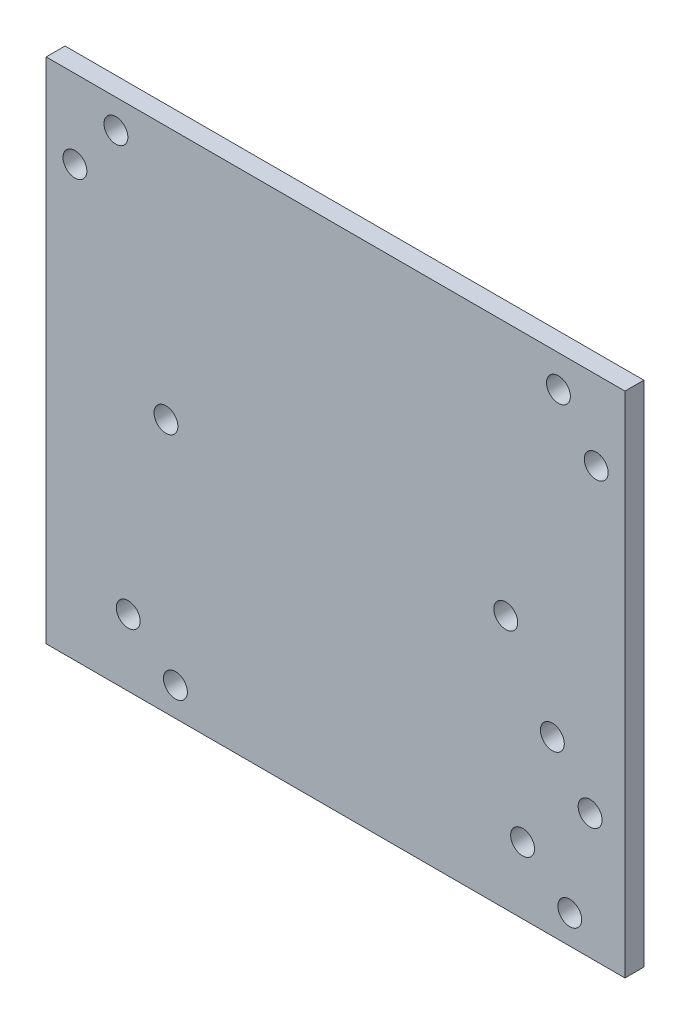
SolidWorks part; units mm, degrees
ref_plane "Front Plane" through (0, 0, 0) normal (0, 0, 1) x (1, 0, 0)
ref_plane "Top Plane" through (0, 0, 0) normal (0, 1, 0) x (1, 0, 0)
ref_plane "Right Plane" through (0, 0, 0) normal (1, 0, 0) x (0, 0, -1)
sketch "Sketch1" plane through (0, 0, 0) normal (0, 0, 1) x (1, 0, 0)
  line L0 (959.4886, 308.695) -> (959.4886, 257.3944) construction
  line L1 (959.4886, 234.6614) -> (959.4886, 406.5207) construction
  line L2 (862.0448, 217.2783) -> (1056.7178, 217.2783)
  line L3 (862.0448, 217.2783) -> (862.0448, 388.2332)
  line L4 (862.0448, 388.2332) -> (1056.7178, 388.2332)
  line L5 (1056.7178, 217.2783) -> (1056.7178, 388.2332)
  line L6 (902.3386, 302.7557) -> (1016.6386, 302.7557) construction
  circle A0 centre (1022.28, 239.6533) radius 2.5273 construction
  circle A1 centre (1038.155, 226.9533) radius 2.5273 construction
  circle A2 centre (889.6448, 239.6533) radius 2.5273 construction
  circle A3 centre (1034.3339, 377.4809) radius 2.5273 construction
  circle A4 centre (1047.0428, 361.6131) radius 2.5273 construction
  circle A5 centre (871.7198, 361.7933) radius 2.5273 construction
  circle A6 centre (885.5053, 378.5582) radius 2.5273 construction
  circle A7 centre (1022.28, 239.6533) radius 2.5273 construction
  circle A8 centre (1038.155, 226.9533) radius 2.5273 construction
  circle A9 centre (889.6448, 239.6533) radius 2.5273 construction
  circle A10 centre (1034.3339, 377.4809) radius 2.5273 construction
  circle A11 centre (1047.0428, 361.6131) radius 2.5273 construction
  circle A12 centre (871.7198, 361.7933) radius 2.5273 construction
  circle A13 centre (885.5053, 378.5582) radius 2.5273 construction
  circle A14 centre (905.5198, 226.9533) radius 2.5273 construction
  circle A15 centre (905.5198, 226.9533) radius 2.5273 construction
  circle A16 centre (1022.28, 239.6533) radius 4.0127
  circle A17 centre (1038.155, 226.9533) radius 4.0127
  circle A18 centre (889.6448, 239.6533) radius 4.0127
  circle A19 centre (1034.3339, 377.4809) radius 4.0127
  circle A20 centre (1047.0428, 361.6131) radius 4.0127
  circle A21 centre (871.7198, 361.7933) radius 4.0127
  circle A22 centre (885.5053, 378.5582) radius 4.0127
  circle A23 centre (905.5198, 226.9533) radius 4.0127
  circle A24 centre (885.5053, 378.5582) radius 6.5 construction
  circle A25 centre (871.7198, 361.7933) radius 6.5 construction
  circle A26 centre (889.6448, 239.6533) radius 6.5 construction
  circle A27 centre (905.5198, 226.9533) radius 6.5 construction
  circle A28 centre (1022.28, 239.6533) radius 6.5 construction
  circle A29 centre (1038.155, 226.9533) radius 6.5 construction
  circle A30 centre (1047.0428, 361.6131) radius 6.5 construction
  circle A31 centre (1034.3339, 377.4809) radius 6.5 construction
  circle A32 centre (-682.1218, 370.9328) radius 4.0127 construction
  circle A33 centre (902.3386, 302.7557) radius 4.0127
  circle A34 centre (-672.6612, 269.9726) radius 4.0132 construction
  circle A35 centre (-672.6612, 269.9726) radius 4.0132 construction
  circle A36 centre (1016.6386, 302.7557) radius 4.0127
  circle A37 centre (1044.9866, 259.4145) radius 2.5273 construction
  circle A38 centre (1032.2866, 275.2895) radius 2.5273 construction
  circle A39 centre (1044.9866, 259.4145) radius 2.5273 construction
  circle A40 centre (1032.2866, 275.2895) radius 2.5273 construction
  circle A41 centre (1032.2866, 275.2895) radius 4.0254
  circle A42 centre (1044.9866, 259.4145) radius 4.0254
  point P60 (959.4886, 302.7557)
  point P76 (862.0448, 302.7557)
  dimension "D2" = 114.3
  dimension "D1" = 13
  dimension "D3" = 3.175
  dimension "D4" = 3.175
  dimension "D5" = 3.175
  dimension "D6" = 3.175
  dimension "D7" = 8.0508
extrude "Boss-Extrude1" add sketch "Sketch1" along normal blind 6.35
